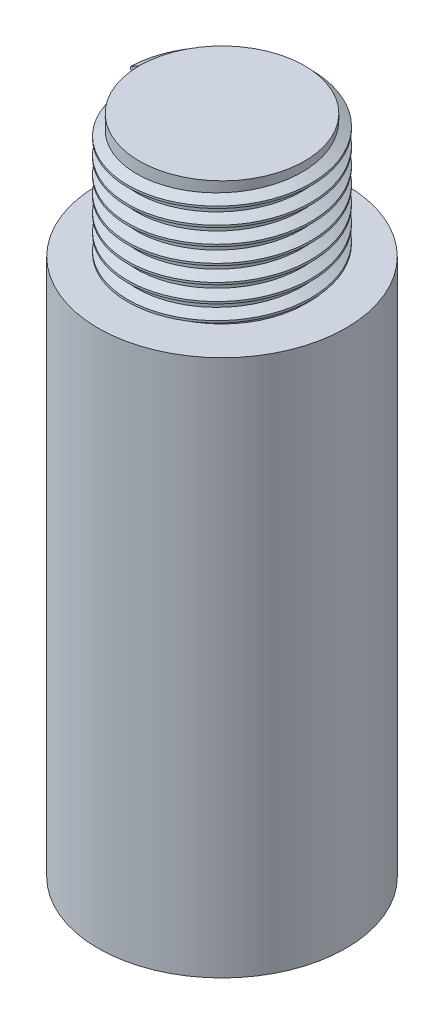
SolidWorks part; units mm, degrees
ref_plane "Front Plane" through (0, 0, 0) normal (0, 0, 1) x (1, 0, 0)
ref_plane "Top Plane" through (0, 0, 0) normal (0, 1, 0) x (1, 0, 0)
ref_plane "Right Plane" through (0, 0, 0) normal (1, 0, 0) x (0, 0, -1)
sketch "Sketch1" plane through (0, 0, 0) normal (0, 0, 1) x (1, 0, 0)
  line L0 (0, 0) -> (0, 50.8) construction
  line L1 (0, 0) -> (9.525, 0)
  line L2 (9.525, 0) -> (9.525, 41.275)
  line L3 (9.525, 41.275) -> (6.35, 41.275)
  line L4 (6.35, 41.275) -> (6.35, 50.8)
  line L5 (6.35, 50.8) -> (0, 50.8)
  line L6 (0, 0) -> (0, 50.8)
  dimension "D1" = 50.8
  dimension "D2" = 9.525
  dimension "D3" = 6.35
  dimension "D4" = 9.525
revolve "Revolve1" add sketch "Sketch1" angle 360 about L0
thread "Thread1" pitch 1.27 method extrude profile "Thread Profile2" start angle 0, offset 0, length 10, pitch 1.27, diameter 12.7
ref_plane "Plane2" through (-6.35, 50.8, 0) normal (0, 0, 1) x (-1, 0, 0)
sketch "Thread Profile2" plane through (-6.35, 50.8, 0) normal (0, 0, 1) x (-1, 0, 0)
  line L0 (0, 0) -> (0, 1.27) construction
  line L1 (0, 0) -> (0.6874, 0.3969)
  line L2 (0.6874, 0.3969) -> (0.6874, 0.5556)
  line L3 (0.6874, 0.5556) -> (0, 0.9525)
  line L4 (0.6874, 0.4762) -> (0, 0.4762) construction
  line L11 (0, 0) -> (0, 0.9525)
  point P2 (0, 0)
  dimension "Pitch" = 1.27
  dimension "Profile_Angle" = 60
  dimension "Profile_Land" = 0.1588
  dimension "Profile_Height" = 0.6874
